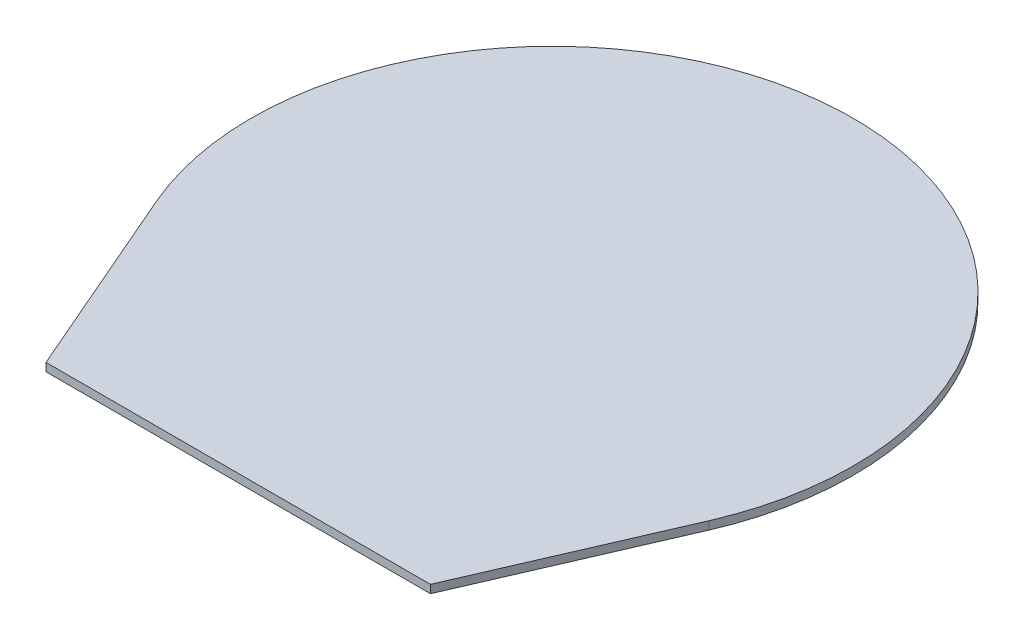
SolidWorks part; units mm, degrees
ref_plane "Front Plane" through (0, 0, 0) normal (0, 0, 1) x (1, 0, 0)
ref_plane "Top Plane" through (0, 0, 0) normal (0, 1, 0) x (1, 0, 0)
ref_plane "Right Plane" through (0, 0, 0) normal (1, 0, 0) x (0, 0, -1)
sketch "Sketch1" plane through (0, 0, 0) normal (0, 1, 0) x (1, 0, 0)
  circle A0 centre (0, 0) radius 117.5
  dimension "D1" = 235
extrude "Boss-Extrude1" add sketch "Sketch1" along normal blind 3.175
sketch "Sketch4" plane through (0, 0, 0) normal (0, 1, 0) x (1, 0, 0)
  line L2 (0, 0) -> (0, -53.2962) construction
  line L5 (107.8261, -46.6881) -> (75, -122.5)
  line L6 (75, -122.5) -> (-75, -122.5)
  line L7 (-75, -122.5) -> (-107.8261, -46.6881)
  line L8 (-107.8261, -46.6881) -> (107.8261, -46.6881)
  line L9 (0, -122.5) -> (0, -117.5) construction
  circle A3 centre (0, 0) radius 117.5 construction
  circle A4 centre (0, 0) radius 117.5 construction
  dimension "D1" = 150
  dimension "D2" = 5
extrude "Boss-Extrude2" add sketch "Sketch4" along normal up to surface (3.175 mm away) contours L5 | L8 L7 L6 L5 region at (0, 0, 82.3254) up to face at (0, 3.175, 117.5)
sketch "Sketch5" plane through (0, 0, 0) normal (0, 1, 0) x (1, 0, 0)
  line L0 (75, 117.5) -> (-0.1661, 117.5)
  line L1 (75, 117.5) -> (106.5777, 49.4717)
  line L2 (0, 0) -> (0, 46.0662) construction
  line L3 (-75, 117.5) -> (-0.1661, 117.5)
  line L4 (-75, 117.5) -> (-106.5777, 49.4717)
  circle A0 centre (0, 0) radius 117.5 construction
  arc A1 (106.5777, 49.4717) -> (-106.5777, 49.4717) centre (0, 0) ccw
  dimension "D1" = 150
extrude "Boss-Extrude3" [suppressed] add sketch "Sketch5" along normal up to surface (3.175 mm away) contours A1 L1 L0 | A1 L0 L3 L4 up to face at (0, 3.175, 43.547)
